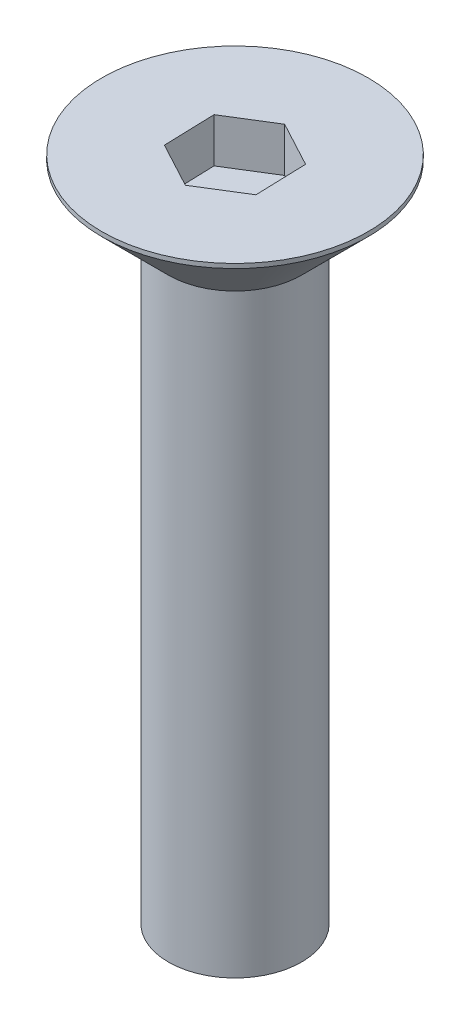
SolidWorks part; units mm, degrees
ref_plane "前视基准面" through (0, 0, 0) normal (0, 0, 1) x (1, 0, 0)
ref_plane "上视基准面" through (0, 0, 0) normal (0, 1, 0) x (1, 0, 0)
ref_plane "右视基准面" through (0, 0, 0) normal (1, 0, 0) x (0, 0, -1)
sketch "草图1" plane through (0, 0, 0) normal (0, 1, 0) x (1, 0, 0)
  circle A0 centre (0, 0) radius 1.5
  dimension "D1" = 3
extrude "凸台-拉伸1" add sketch "草图1" along normal blind 12
sketch "草图2" plane through (0, 12, 0) normal (0, 1, 0) x (1, 0, 0)
  circle A0 centre (0, 0) radius 3
  dimension "D1" = 6
extrude "凸台-拉伸2" add sketch "草图2" along normal blind 3
chamfer "倒角1" distance 2.9 angle 45 1 edges at (0, 12, 3)
sketch "草图3" plane through (0, 15, 0) normal (0, 1, 0) x (1, 0, 0)
  line L1 (1.0175, -0.5459) -> (0.9815, 0.6083)
  line L2 (0.9815, 0.6083) -> (-0.036, 1.1541)
  line L3 (-0.036, 1.1541) -> (-1.0175, 0.5459)
  line L4 (-1.0175, 0.5459) -> (-0.9815, -0.6083)
  line L5 (-0.9815, -0.6083) -> (0.036, -1.1541)
  line L6 (0.036, -1.1541) -> (1.0175, -0.5459)
  circle A0 centre (0, 0) radius 1 construction
  point P1 (0.9995, 0.0312)
  dimension "D1" = 2
extrude "切除-拉伸1" cut sketch "草图3" against normal blind 1
